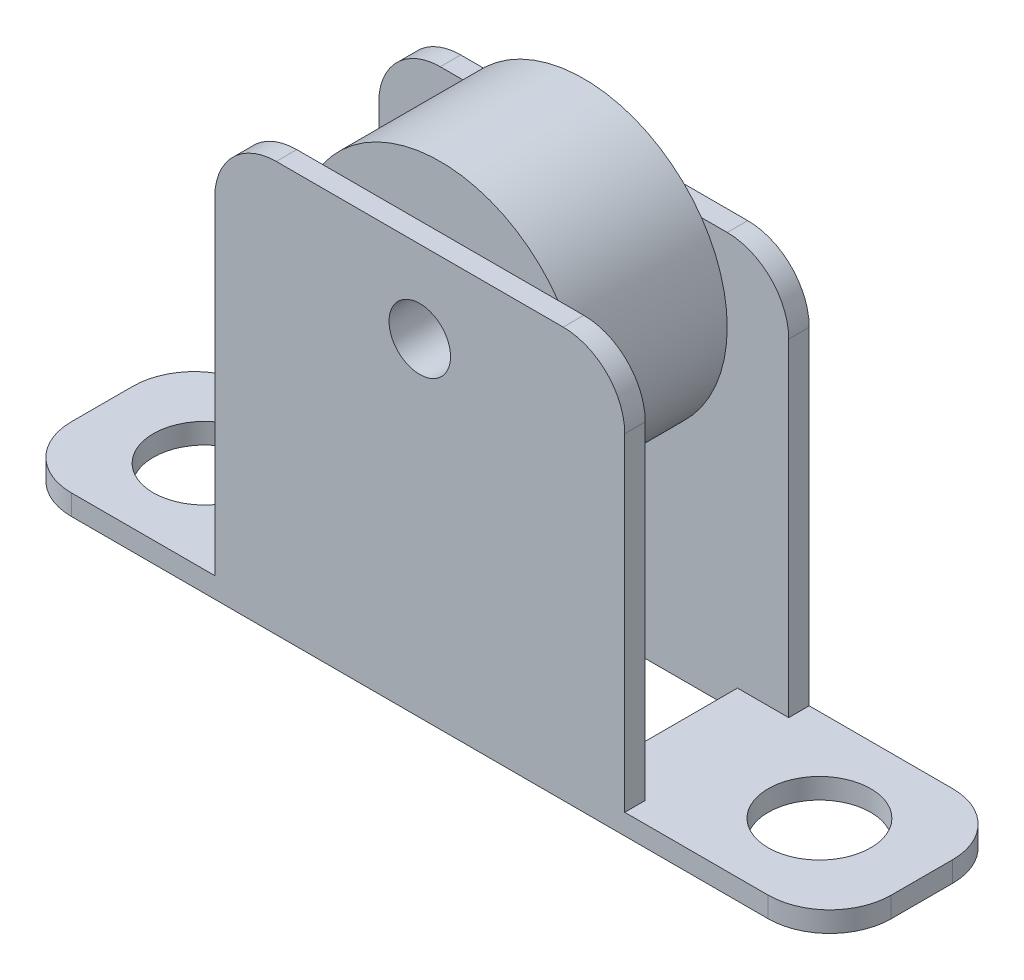
SolidWorks part; units mm, degrees
ref_plane "前视基准面" through (0, 0, 0) normal (0, 0, 1) x (1, 0, 0)
ref_plane "上视基准面" through (0, 0, 0) normal (0, 1, 0) x (1, 0, 0)
ref_plane "右视基准面" through (0, 0, 0) normal (1, 0, 0) x (0, 0, -1)
sketch "草图1" plane through (0, 0, 0) normal (0, 1, 0) x (1, 0, 0)
  line L0 (0, 4.5) -> (40, 4.5) construction
  line L1 (0, 0) -> (40, 0)
  line L2 (0, 0) -> (0, 9)
  line L3 (0, 9) -> (40, 9)
  line L4 (40, 0) -> (40, 9)
  line L5 (20, 0) -> (20, 9) construction
  line L6 (12.5, 8) -> (27.5, 8)
  line L7 (12.5, 8) -> (12.5, 1)
  line L8 (12.5, 1) -> (27.5, 1)
  line L9 (27.5, 8) -> (27.5, 1)
  dimension "D1" = 9
  dimension "D2" = 40
  dimension "D3" = 1
  dimension "D4" = 15
extrude "凸台-拉伸1" add sketch "草图1" along normal blind 1
sketch "草图2" plane through (0, 0, 0) normal (0, 0, 1) x (1, 0, 0)
  line L0 (0, 0) -> (40, 0) construction
  line L1 (10, 0) -> (30, 0)
  line L2 (10, 0) -> (10, 20)
  line L3 (10, 20) -> (30, 20)
  line L4 (30, 0) -> (30, 20)
  line L5 (20, 0) -> (20, 17.2968) construction
  circle A0 centre (20, 16) radius 1.5
  dimension "D3" = 3
  dimension "D4" = 4
  dimension "D1" = 20
  dimension "D2" = 20
extrude "凸台-拉伸2" add sketch "草图2" against normal blind 1
extrude "凸台-拉伸3" add sketch "草图2<2>" along normal blind 1 from surface starting at face at (20, 0.5, -9)
sketch "草图2<2>" plane through (0, 0, 0) normal (0, 0, 1) x (1, 0, 0) same geometry as "草图2"
hole_wizard "Ø5.0 (5) 直径孔1" positions "草图3" profile "草图4" hole size "Ø5.0" standard "GB"
sketch "草图3" plane through (0, 1, 0) normal (0, 1, 0) x (1, 0, 0)
  line L0 (0, 4.5) -> (40, 4.5) construction
  line L1 (0, 9) -> (0, 0) construction
  line L2 (40, 0) -> (40, 9) construction
  point P8 (5, 4.5)
  point P10 (35, 4.5)
  dimension "D1" = 5
  dimension "D2" = 5
sketch "草图4" plane through (35, 1, -4.5) normal (1, 0, 0) x (0, 0, 1)
  line L0 (0, 0) -> (0, 6)
  line L1 (0, 6) -> (2.5, 6)
  line L2 (2.5, 6) -> (2.5, 0)
  line L5 (2.5, 0) -> (0, 0)
  line L10 (0, 6) -> (-2.5, 6) construction
  line L11 (0, -6.35) -> (0, 107.95) construction
  dimension "孔直径" = 5
  dimension "孔深度" = 6
  dimension "导头角度" = 180
sketch "草图5" plane through (0, 0, -8) normal (0, 0, 1) x (1, 0, 0)
  circle A0 centre (20, 16) radius 7
  circle A1 centre (20, 16) radius 1.5 construction
  circle A2 centre (20, 16) radius 1.5
  dimension "D1" = 14
extrude "凸台-拉伸4" add sketch "草图5" along normal up to surface (7 mm away) up to face at (20, 5.5, -1)
fillet "圆角1" radius 3 8 edges at (40, 0.5, 0) (40, 0.5, -9) (0, 0.5, -9) (0, 0.5, 0) (30, 20, -0.5) (30, 20, -8.5) (10, 20, -8.5) (10, 20, -0.5)
ref_plane "基准面1" through (0, 0, -4.5) normal (0, 0, 1) x (1, 0, 0)
sketch "草图6" plane through (0, 0, -4.5) normal (0, 0, 1) x (1, 0, 0)
  arc A1 (14.2554, 20) -> (25.7446, 20) centre (20, 16) ccw construction
  circle A3 centre (20, 16) radius 7
